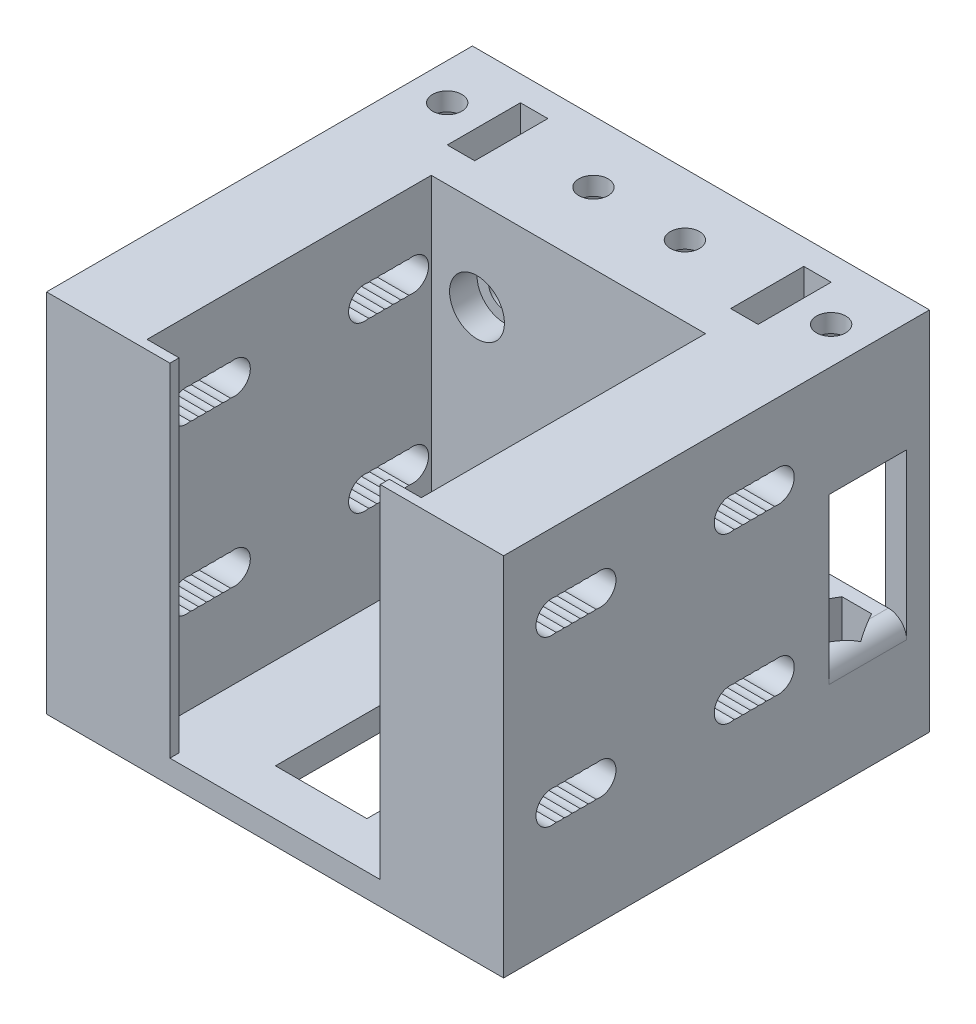
SolidWorks part; units mm, degrees
ref_plane "Front Plane" through (0, 0, 0) normal (0, 0, 1) x (1, 0, 0)
ref_plane "Top Plane" through (0, 0, 0) normal (0, 1, 0) x (1, 0, 0)
ref_plane "Right Plane" through (0, 0, 0) normal (1, 0, 0) x (0, 0, -1)
sketch "Sketch1" plane through (0, 0, 0) normal (0, 1, 0) x (1, 0, 0)
  line L1 (0, 0) -> (50, 0)
  line L2 (0, 0) -> (0, 15)
  line L3 (0, 15) -> (50, 15)
  line L4 (50, 0) -> (50, 15)
  dimension "D1" = 15
  dimension "D2" = 50
extrude "Main_Body" add sketch "Sketch1" along normal blind 40
sketch "Sketch2" plane through (0, 0, -15) normal (0, 0, -1) x (-1, 0, 0)
  line L0 (0, 20) -> (-50, 20) construction
  line L1 (-50, 40) -> (0, 40)
  line L2 (-50, 40) -> (-50, 0)
  line L3 (-50, 0) -> (0, 0)
  line L4 (0, 40) -> (0, 0)
  line L5 (-47.7, 33.7) -> (-2.3, 33.7)
  line L6 (-47.7, 33.7) -> (-47.7, 6.3)
  line L7 (-47.7, 6.3) -> (-2.3, 6.3)
  line L8 (-2.3, 33.7) -> (-2.3, 6.3)
  line L9 (-25, 40) -> (-25, 0) construction
  point P12 (-2.3, 20)
  point P16 (-25, 33.7)
  dimension "D1" = 27.4
  dimension "2.3" = 2.3
extrude "Carraige_Mount" add sketch "Sketch2" along normal blind 2.5
sketch "Sketch3" plane through (0, 0, 0) normal (0, 0, 1) x (1, 0, 0)
  line L0 (15, 10) -> (35, 10) construction
  line L1 (35, 10) -> (35, 30) construction
  line L2 (15, 10) -> (15, 30) construction
  line L3 (15, 30) -> (35, 30) construction
  line L4 (15, 10) -> (35, 30) construction
  line L5 (0, 40) -> (50, 0) construction
  circle A0 centre (15, 30) radius 1.75
  circle A1 centre (35, 30) radius 1.75
  circle A2 centre (35, 10) radius 1.75
  circle A3 centre (15, 10) radius 1.75
  point P12 (25, 20)
  point P13 (25, 20)
  dimension "D1" = 3.5
  dimension "D2" = 3.5
  dimension "D3" = 3.5
  dimension "D4" = 3.5
  dimension "D5" = 20
  dimension "D6" = 20
extrude "Carraige_Screw_Holes" cut sketch "Sketch3" against normal blind 15
sketch "Sketch6" plane through (0, 0, 0) normal (0, 0, 1) x (1, 0, 0)
  line L0 (0, 40) -> (0, 0)
  line L1 (0, 0) -> (50, 0)
  line L2 (50, 0) -> (50, 40)
  line L3 (50, 40) -> (40, 40)
  line L5 (40, 40) -> (40, 2.5767)
  line L6 (40, 2.5767) -> (10, 2.5767)
  line L7 (10, 2.5767) -> (10, 40)
  line L8 (10, 40) -> (0, 40)
  line L9 (10, 40) -> (40, 40) construction
  line L10 (0, 20) -> (50, 20) construction
  line L11 (25, 0) -> (25, 40) construction
  point P18 (25, 40)
  dimension "D1" = 30
  dimension "D2" = 40
  dimension "D3" = 37.4233
extrude "LA_Cutout" add sketch "Sketch6" along normal blind 28.09
sketch "Sketch7" plane through (0, 0, 28.09) normal (0, 0, 1) x (1, 0, 0)
  line L0 (40, 2.5767) -> (10, 2.5767) construction
  line L2 (0, 40) -> (0, 0)
  line L3 (0, 0) -> (50, 0)
  line L4 (50, 40) -> (50, 0)
  line L6 (13.5, 40) -> (13.5, 2.5767)
  line L7 (13.5, 2.5767) -> (36.5, 2.5767)
  line L8 (36.5, 40) -> (36.5, 2.5767)
  line L9 (0, 40) -> (13.5, 40)
  line L10 (50, 40) -> (36.5, 40)
  line L11 (13.5, 40) -> (36.5, 40) construction
  line L12 (50, 40) -> (0, 40) construction
  line L15 (50, 40) -> (40, 40) construction
  point P12 (25, 2.5767)
  point P15 (25, 2.5767)
  point P16 (25, 40)
  point P25 (25, 40)
  dimension "D1" = 23
extrude "Front_Wall" add sketch "Sketch7" along normal blind 1
sketch "Sketch9" plane through (0, 2.5767, 0) normal (0, 1, 0) x (1, 0, 0)
  line L0 (10, -28.09) -> (40, 0) construction
  line L1 (40, -28.09) -> (40, 0) construction
  line L2 (20, -4.045) -> (30, -24.045) construction
  line L3 (20, -4.045) -> (30, -4.045)
  line L4 (20, -4.045) -> (20, -24.045)
  line L5 (20, -24.045) -> (30, -24.045)
  line L6 (30, -4.045) -> (30, -24.045)
  point P5 (25, -14.045)
  point P6 (25, -14.045)
  dimension "D1" = 10
  dimension "D2" = 20
extrude "LA_Through_Hole" cut sketch "Sketch9" against normal blind 3
sketch "Sketch10" plane through (0, 0, 0) normal (-1, 0, 0) x (0, 0, 1)
  line L0 (-15, 28) -> (-15, 12)
  line L1 (-15, 12) -> (-6.5, 12)
  line L4 (-10.75, 12) -> (-10.75, 28) construction
  line L5 (-17.5, 20) -> (-10.75, 20) construction
  line L6 (-17.5, 0) -> (-17.5, 40) construction
  line L14 (-6.5, 28) -> (-6.5, 12)
  line L15 (-15, 28) -> (-6.5, 28)
  point P5 (-10.75, 28)
  point P12 (-10.75, 20)
  dimension "D1" = 6.75
  dimension "D2" = 16
  dimension "D6" = 4.25
extrude "Belt_Hole" cut sketch "Sketch10" against normal blind 50
ref_plane "Belt_Mount_Mirror_Plane" through (25, 0, 0) normal (-1, 0, 0) x (0, 0, 1)
sketch "Sketch14" plane through (0, 0, 0) normal (0, 0, 1) x (1, 0, 0)
  circle A0 centre (15, 30) radius 3
  circle A1 centre (35, 30) radius 3
  circle A2 centre (35, 10) radius 3
  circle A3 centre (15, 10) radius 3
  dimension "D1" = 6
  dimension "D2" = 6
  dimension "D3" = 6
  dimension "D4" = 6
extrude "Carraige_Screw_Heads" cut sketch "Sketch14" against normal blind 6
sketch "Sketch15" plane through (0, 40, 0) normal (0, 1, 0) x (1, 0, 0)
  line L1 (8, 14.75) -> (11, 14.75)
  line L2 (8, 14.75) -> (8, 6.75)
  line L3 (8, 6.75) -> (11, 6.75)
  line L4 (11, 14.75) -> (11, 6.75)
  line L6 (0, 17.5) -> (50, 17.5) construction
  line L7 (0, 15) -> (0, 6.5) construction
  dimension "D1" = 8
  dimension "D2" = 3
  dimension "D4" = 2.75
  dimension "D5" = 8
extrude "Left_Belt_Slot" cut sketch "Sketch15" against normal blind 14
sketch "Sketch19" plane through (0, 40, 0) normal (0, 1, 0) x (1, 0, 0)
  line L0 (0, 10.7423) -> (50, 10.7423) construction
  line L1 (0, 17.5) -> (0, -29.09) construction
  line L2 (50, -29.09) -> (50, 17.5) construction
  circle A0 centre (4, 10.7423) radius 1.6
  circle A1 centre (20, 10.7423) radius 1.6
  dimension "D1" = 4
  dimension "D2" = 3.2
  dimension "D3" = 3.2
  dimension "D4" = 16
extrude "Belt_Mount_Screw_Holes" cut sketch "Sketch19" against normal blind 14
sketch "Sketch20" plane through (0, 28, 0) normal (0, -1, 0) x (1, 0, 0)
  line L0 (20, -10.7423) -> (23.2332, -10.7423) construction
  line L1 (18.3834, -13.5423) -> (21.6166, -13.5423)
  line L2 (21.6166, -13.5423) -> (23.2332, -10.7423)
  line L3 (23.2332, -10.7423) -> (21.6166, -7.9423)
  line L4 (21.6166, -7.9423) -> (18.3834, -7.9423)
  line L5 (18.3834, -7.9423) -> (16.7668, -10.7423)
  line L6 (16.7668, -10.7423) -> (18.3834, -13.5423)
  line L7 (7.2332, -10.7423) -> (5.6166, -7.9423)
  line L8 (5.6166, -7.9423) -> (2.3834, -7.9423)
  line L9 (2.3834, -7.9423) -> (0.7668, -10.7423)
  line L10 (0.7668, -10.7423) -> (2.3834, -13.5423)
  line L11 (2.3834, -13.5423) -> (5.6166, -13.5423)
  line L12 (5.6166, -13.5423) -> (7.2332, -10.7423)
  line L13 (4, -10.7423) -> (7.2332, -10.7423) construction
  circle A0 centre (20, -10.7423) radius 2.8 construction
  circle A1 centre (4, -10.7423) radius 2.8 construction
  dimension "D1" = 5.6
  dimension "D2" = 5.6
extrude "Belt_Mount_Nut_Holes" cut sketch "Sketch20" against normal blind 10 and the other way blind 30
mirror "Belt_Mount_Mirror" about plane through (25, 0, 0) normal (-1, 0, 0) of "Belt_Mount_Screw_Holes", "Belt_Mount_Nut_Holes", "Left_Belt_Slot"
fillet "Fillet1" radius 2 2 edges at (0, 12, -10.75) (50, 12, -10.75)
sketch "Sketch8" plane through (40, 0, 0) normal (-1, 0, 0) x (0, 0, 1)
  line L0 (4.295, 31.5767) -> (4.295, 13.5767) construction
  line L1 (4.295, 13.5767) -> (23.795, 13.5767) construction
  line L2 (23.795, 13.5767) -> (23.795, 31.5767) construction
  line L3 (23.795, 31.5767) -> (4.295, 31.5767) construction
  line L4 (4.295, 13.5767) -> (23.795, 31.5767) construction
  line L6 (28.09, 40) -> (0, 40) construction
  line L7 (28.09, 2.5767) -> (0, 2.5767) construction
  line L8 (0, 22.5767) -> (28.09, 22.5767) construction
  line L9 (0, 40) -> (0, 2.5767) construction
  line L10 (28.09, 40) -> (28.09, 2.5767) construction
  circle A0 centre (4.295, 31.5767) radius 1.75
  circle A1 centre (23.795, 31.5767) radius 1.75
  circle A2 centre (4.295, 13.5767) radius 1.75
  circle A3 centre (23.795, 13.5767) radius 1.75
  point P18 (14.045, 22.5767)
  point P19 (14.045, 22.5767)
  dimension "D1" = 3.5
  dimension "D2" = 3.5
  dimension "D3" = 3.5
  dimension "D4" = 3.5
  dimension "D7" = 11
  dimension "D5" = 19.5
  dimension "D6" = 18
  dimension "D8" = 8.4233
extrude "LA_Screw_Holes" cut sketch "Sketch8" against normal blind 10 and the other way blind 40
sketch "Sketch21" plane through (0, 0, 0) normal (0, 0, 1) x (1, 0, 0)
  line L1 (10, 2.5767) -> (40, 2.5767)
  line L2 (10, 2.5767) -> (10, 40)
  line L3 (10, 40) -> (40, 40)
  line L4 (40, 2.5767) -> (40, 40)
extrude "Cut-Extrude1" cut sketch "Sketch21" against normal blind 3
pattern_linear "LPattern1" count 7 spacing 0.875 along (0, 0, -1) of "LA_Screw_Holes"
